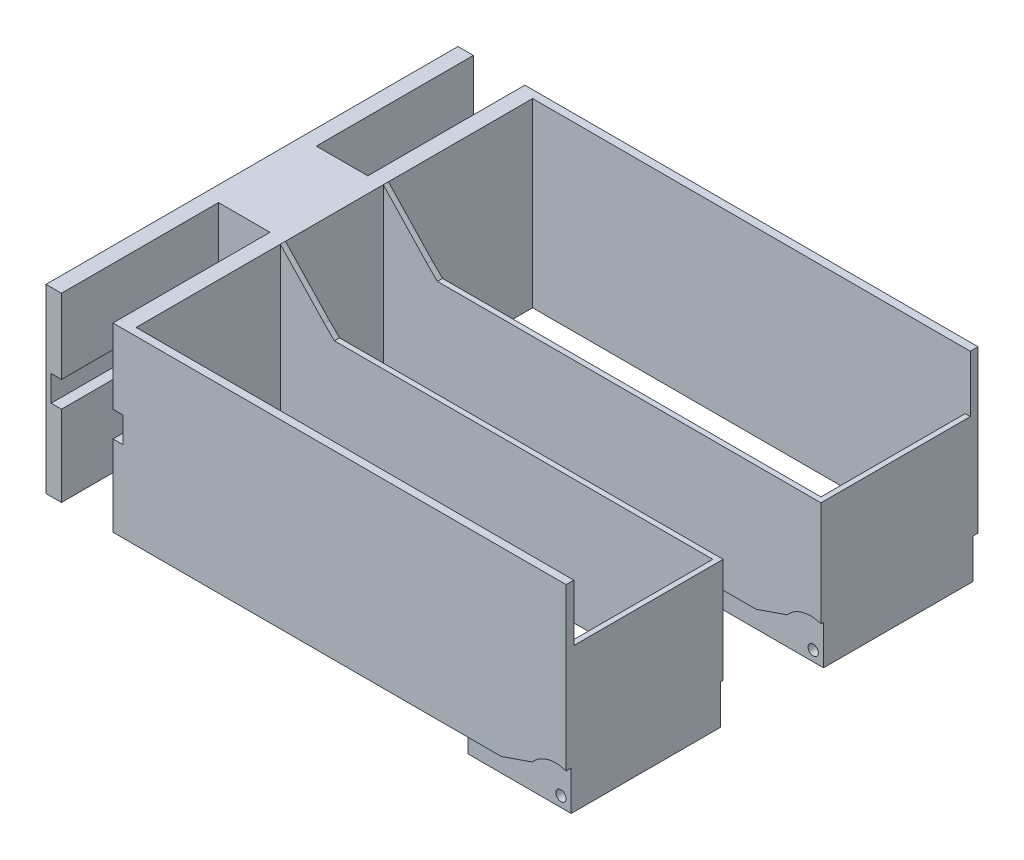
SolidWorks part; units mm, degrees
ref_plane "Front Plane" through (0, 0, 0) normal (0, 0, 1) x (1, 0, 0)
ref_plane "Top Plane" through (0, 0, 0) normal (0, 1, 0) x (1, 0, 0)
ref_plane "Right Plane" through (0, 0, 0) normal (1, 0, 0) x (0, 0, -1)
sketch "Sketch4" plane through (0, 0, 0) normal (0, 0, 1) x (1, 0, 0)
  line L1 (-42.5, -19.5) -> (42.5, -19.5)
  line L2 (-42.5, -19.5) -> (-42.5, 19.5)
  line L3 (-42.5, 19.5) -> (42.5, 19.5)
  line L4 (42.5, -19.5) -> (42.5, 19.5)
  line L5 (-42.5, -19.5) -> (42.5, 19.5) construction
  line L6 (-42.5, 19.5) -> (42.5, -19.5) construction
  point P0 (0, 0)
  dimension "D1" = 39
  dimension "D2" = 85
extrude "Boss-Extrude2" add sketch "Sketch4" along normal blind 30
sketch "Angled cut" plane through (0, 0, 30) normal (0, 0, 1) x (1, 0, 0)
  line L7 (12.07, 10.5) -> (42.5, 10.5)
  line L8 (42.5, -19.5) -> (42.5, 19.5) construction
  line L9 (42.5, 10.5) -> (42.5, 19.5)
  line L10 (42.5, 19.5) -> (-42.5, 19.5)
  line L11 (12.07, 10.5) -> (-34, 10.5)
  line L12 (-42.5, 19.5) -> (-34, 10.5)
  dimension "D1" = 9
  dimension "D2" = 30.43
sketch "Sketch6" plane through (0, 19.5, 0) normal (0, 1, 0) x (1, 0, 0)
  line L1 (42.5, 0) -> (-42.5, 0) construction
  line L2 (-4.9101, 0) -> (-4.9101, 1)
  line L3 (-4.9101, 1) -> (-43.5, 1)
  line L4 (-43.5, 1) -> (-43.5, -30)
  line L5 (-42.5, -30) -> (-43.5, -30)
  line L6 (-42.5, -30) -> (-42.5, 0)
  line L7 (-42.5, 0) -> (-4.9101, 0)
  dimension "D1" = 1
  dimension "D2" = 1
extrude "Boss-Extrude3" add sketch "Sketch6" against normal blind 39
sketch "Sketch7" plane through (0, 19.5, 0) normal (0, 1, 0) x (1, 0, 0)
  line L0 (-0.5, -30) -> (-0.5, -15) construction
  line L1 (42.5, -30) -> (-43.5, -30) construction
  line L2 (42.5, -15) -> (-0.5, -15) construction
  line L3 (42.5, -30) -> (42.5, 0) construction
  line L4 (42.5, 0) -> (-4.9101, 0) construction
  line L5 (-42.5, -29) -> (41.5, -29)
  line L6 (-42.5, -29) -> (-42.5, -1)
  line L7 (-42.5, -1) -> (41.5, -1)
  line L8 (41.5, -29) -> (41.5, -1)
  line L9 (-42.5, -29) -> (41.5, -1) construction
  line L10 (-42.5, -1) -> (41.5, -29) construction
  dimension "D1" = 1
  dimension "D2" = 1
extrude "Cut-Extrude1" cut sketch "Sketch7" against normal blind 39
extrude "Cut-Extrude2" cut sketch "Angled cut" against normal blind 1 contours L7 L9 L10 L12 L11
sketch "Sketch9" plane through (0, 0, 29) normal (0, 0, 1) x (1, 0, 0)
  line L1 (41.5, 19.5) -> (42.5, 19.5)
  line L2 (41.5, 19.5) -> (41.5, 10.5)
  line L3 (41.5, 10.5) -> (42.5, 10.5)
  line L4 (42.5, 19.5) -> (42.5, 10.5)
extrude "Cut-Extrude4" cut sketch "Sketch9" against normal up to vertex (28 mm away) up to point (41.5, 19.5, 1)
sketch "Sketch19" plane through (-43.5, 0, 0) normal (-1, 0, 0) x (0, 0, 1)
  line L1 (-1, 19.5) -> (30, 19.5)
  line L2 (-1, 19.5) -> (-1, -19.5)
  line L3 (-1, -19.5) -> (30, -19.5)
  line L4 (30, 19.5) -> (30, -19.5)
extrude "Boss-Extrude4" add sketch "Sketch19" along normal blind 2
sketch "Sketch20" plane through (0, 0, 30) normal (0, 0, 1) x (1, 0, 0)
  line L1 (-45.5, 19.5) -> (-42.5, 19.5)
  line L2 (-45.5, 19.5) -> (-45.5, -19.5)
  line L3 (-45.5, -19.5) -> (-42.5, -19.5)
  line L4 (-42.5, 19.5) -> (-42.5, -19.5)
extrude "Boss-Extrude5" add sketch "Sketch20" along normal blind 9
sketch "Sketch38" plane through (0, 10.5, 0) normal (0, 1, 0) x (1, 0, 0)
  line L1 (42.5, -30) -> (41.5, -30)
  line L2 (42.5, -30) -> (42.5, -1)
  line L3 (42.5, -1) -> (41.5, -1)
  line L4 (41.5, -30) -> (41.5, -1)
extrude "Boss-Extrude6" add sketch "Sketch38" along normal up to vertex (9 mm away) up to point (42.5, 19.5, 1)
sketch "Sketch39" plane through (-4.9101, 0, 0) normal (1, 0, 0) x (0, 0, -1)
  line L1 (1, 19.5) -> (0, 19.5)
  line L2 (1, 19.5) -> (1, -19.5)
  line L3 (1, -19.5) -> (0, -19.5)
  line L4 (0, 19.5) -> (0, -19.5)
extrude "Boss-Extrude7" add sketch "Sketch39" along normal up to vertex (47.4101 mm away) up to point (42.5, 19.5, 0)
sketch "Sketch40" plane through (0, 0, 29) normal (0, 0, -1) x (-1, 0, 0)
  line L0 (-42.5, -19.5) -> (-42.5, 0)
  line L1 (-42.5, -19.5) -> (-42.5, 19.5) construction
  line L2 (-42.5, 0) -> (-22.5, -19.5)
  line L3 (-42.5, -19.5) -> (45.5, -19.5) construction
  line L4 (-22.5, -19.5) -> (-42.5, -19.5)
  dimension "D1" = 20
extrude "Boss-Extrude8" add sketch "Sketch40" along normal up to vertex (28 mm away) up to point (41.5, -19.5, 1)
sketch "Sketch42" plane through (0, 0, -1) normal (0, 0, -1) x (-1, 0, 0)
  line L0 (45.5, 19.5) -> (45.5, -19.5) construction
  line L1 (45.5, 0) -> (43.5, 0)
  line L2 (45.5, 0) -> (45.5, 5)
  line L3 (45.5, 5) -> (43.5, 5)
  line L4 (43.5, 0) -> (43.5, 5)
  dimension "D1" = 5
  dimension "D2" = 2
extrude "Cut-Extrude5" cut sketch "Sketch42" against normal blind 30
sketch "Sketch44" plane through (0, 0, -1) normal (0, 0, 1) x (1, 0, 0)
  line L0 (-42.5, -19.5) -> (42.5, -19.5) construction
  line L1 (42.5, -19.5) -> (42.5, 19.5) construction
  circle A0 centre (40.5, -17.5) radius 1
  dimension "D2" = 2
  dimension "D1" = 2
  dimension "D3" = 2
sketch "Sketch45" plane through (0, 0, 30) normal (0, 0, 1) x (1, 0, 0)
  line L0 (-42.5, 19.5) -> (-42.5, -19.5)
  line L1 (-42.5, -19.5) -> (42.5, -19.5)
  line L2 (42.5, -19.5) -> (42.5, 19.5)
  line L3 (42.5, 19.5) -> (41.5, 19.5)
  line L4 (41.5, 19.5) -> (41.5, 10.5)
  line L5 (41.5, 10.5) -> (-34, 10.5)
  line L6 (-34, 10.5) -> (-42.5, 19.5)
extrude "Boss-Extrude9" add sketch "Sketch45" along normal blind 1
extrude "Cut-Extrude7" cut sketch "Sketch44" along normal up to vertex (32 mm away) contours A0 up to point (42.5, -19.5, 31)
sketch "Sketch46" plane through (0, 0, 31) normal (0, 0, 1) x (1, 0, 0)
  line L0 (42.5, -19.5) -> (42.5, 19.5) construction
  line L2 (-42.5, -19.5) -> (42.5, -19.5)
  line L3 (-42.5, -19.5) -> (-42.5, -15.6964)
  line L4 (-42.5, -15.6964) -> (42.5, -15.6964)
  line L5 (42.5, -19.5) -> (42.5, -15.6964)
extrude "Cut-Extrude8" cut sketch "Sketch46" against normal blind 1
sketch "Sketch47" plane through (0, 19.5, 0) normal (0, 1, 0) x (1, 0, 0)
  line L0 (41.5, -15) -> (-45.5, -15) construction
  line L1 (41.5, -29) -> (41.5, -1) construction
  line L2 (-45.5, -39) -> (-45.5, 1) construction
ref_plane "Plane1" through (0, 0, 15) normal (0, 0, 1) x (1, 0, 0)
mirror "Mirror1" about plane through (0, 0, 15) normal (0, 0, 1) of "Cut-Extrude8"
sketch "Sketch48" plane through (0, 0, 29) normal (0, 0, -1) x (-1, 0, 0)
  line L0 (42.5, -15.6964) -> (42.5, -19.5) construction
  line L5 (42.5, -17.5982) -> (-22.5, -17.5982)
  line L6 (42.5, -17.5982) -> (42.5, -19.5)
  line L7 (42.5, -19.5) -> (-22.5, -19.5)
  line L8 (-22.5, -17.5982) -> (-22.5, -19.5)
extrude "Cut-Extrude9" cut sketch "Sketch48" along normal up to vertex (29 mm away) and the other way up to vertex (1 mm away) up to point (-42.5, -19.5, 0) other way up to point (42.5, -19.5, 30)
sketch "Sketch49" plane through (0, 0, -1) normal (0, 0, -1) x (-1, 0, 0)
  circle A0 centre (-40.5, -17.5) radius 6
  dimension "D1" = 12
extrude "Cut-Extrude10" cut sketch "Sketch49" against normal blind 1
chamfer "Chamfer1" distance 5 angle 40 1 edges at (34.7775, -15.6964, -0.5) first distance on face at (38.23, -12.9505, -0.5)
mirror "Mirror5" about plane through (0, 0, 15) normal (0, 0, 1) of "Cut-Extrude10"
chamfer "Chamfer2" distance 5 angle 30 1 edges at (34.7775, -15.6964, 30.5) first distance on face at (-3.8613, -15.6964, 30.5)
sketch "Sketch50" plane through (-42.5, 0, 0) normal (1, 0, 0) x (0, 0, -1)
  line L0 (1, -15.6964) -> (1, -19.5) construction
  line L1 (-30, -17.5982) -> (1, -17.5982)
  line L2 (-30, -17.5982) -> (-30, -19.5)
  line L3 (-30, -19.5) -> (1, -19.5)
  line L4 (1, -17.5982) -> (1, -19.5)
extrude "Cut-Extrude11" cut sketch "Sketch50" against normal up to vertex (3 mm away) up to point (-45.5, -19.5, -1)
sketch "Sketch52" plane through (0, 0, 39) normal (0, 0, 1) x (1, 0, 0)
  line L1 (-45.5, 19.5) -> (-42.5, 19.5)
  line L2 (-45.5, 19.5) -> (-45.5, -19.5)
  line L3 (-45.5, -19.5) -> (-42.5, -19.5)
  line L4 (-42.5, 19.5) -> (-42.5, -19.5)
extrude "Boss-Extrude10" add sketch "Sketch52" along normal blind 0.5
ref_plane "Plane3" through (0, 0, 39.5) normal (0, 0, 1) x (1, 0, 0)
mirror "Mirror8" about plane through (0, 0, 39.5) normal (0, 0, 1) of bodies 151
sketch "Sketch56" plane through (42.5, 0, 0) normal (1, 0, 0) x (0, 0, -1)
  line L0 (-31, 19.5) -> (1, 19.5) construction
  line L1 (-31, -15.6964) -> (-30, -15.6964)
  line L2 (-31, -15.6964) -> (-31, 19.5)
  line L3 (-31, 19.5) -> (-30, 19.5)
  line L4 (-30, -15.6964) -> (-30, 19.5)
extrude "Cut-Extrude13" cut sketch "Sketch56" against normal up to vertex (85 mm away) up to point (-42.5, 19.5, 29)
mirror "Mirror11" about plane through (0, 0, 39.5) normal (0, 0, 1) of "Cut-Extrude13"
sketch "Sketch58" plane through (0, 0, -1) normal (0, 0, -1) x (-1, 0, 0)
  line L0 (-41.5, 19.5) -> (45.5, 19.5) construction
  line L1 (45.5, 19.5) -> (-42.5, 19.5)
  line L2 (45.5, 19.5) -> (45.5, -19.5)
  line L3 (45.5, -19.5) -> (-42.5, -19.5)
  line L4 (-42.5, 19.5) -> (-42.5, -19.5)
extrude "Cut-Extrude14" cut sketch "Sketch58" against normal blind 0.5
sketch "Sketch59" plane through (0, 0, 80) normal (0, 0, 1) x (1, 0, 0)
  line L1 (-45.5, 19.5) -> (42.5, 19.5)
  line L2 (-45.5, 19.5) -> (-45.5, -19.5)
  line L3 (-45.5, -19.5) -> (42.5, -19.5)
  line L4 (42.5, 19.5) -> (42.5, -19.5)
extrude "Cut-Extrude15" cut sketch "Sketch59" against normal blind 0.5
sketch "Sketch60" plane through (-45.5, 0, 0) normal (-1, 0, 0) x (0, 0, 1)
  line L0 (79.5, 19.5) -> (-0.5, 19.5) construction
  line L1 (30, -17.5982) -> (49, -17.5982)
  line L2 (30, -17.5982) -> (30, 19.5)
  line L3 (30, 19.5) -> (49, 19.5)
  line L4 (49, -17.5982) -> (49, 19.5)
extrude "Boss-Extrude11" add sketch "Sketch60" along normal blind 10
sketch "Sketch61" plane through (0, 0, 30) normal (0, 0, -1) x (-1, 0, 0)
  line L1 (55.5, 19.5) -> (58.5, 19.5)
  line L2 (55.5, 19.5) -> (55.5, -17.5982)
  line L3 (55.5, -17.5982) -> (58.5, -17.5982)
  line L4 (58.5, 19.5) -> (58.5, -17.5982)
  dimension "D1" = 3
extrude "Boss-Extrude12" add sketch "Sketch61" along normal up to vertex (30.5 mm away) and the other way up to vertex (49.5 mm away) up to point (-45.5, 5, -0.5) other way up to point (-45.5, 19.5, 79.5)
ref_plane "Plane4" through (-50.5, 0, 0) normal (-1, 0, 0) x (0, 0, 1)
mirror "Mirror12" about plane through (-50.5, 0, 0) normal (-1, 0, 0) of "Cut-Extrude5"
mirror "Mirror13" about plane through (0, 0, 39.5) normal (0, 0, 1) of "Mirror12"
sketch "Sketch63" plane through (0, 0, 0) normal (0, 0, -1) x (-1, 0, 0)
  line L1 (42.5, -15.6964) -> (-42.5, -15.6964)
  line L2 (42.5, -15.6964) -> (42.5, -19.5)
  line L3 (42.5, -19.5) -> (-42.5, -19.5)
  line L4 (-42.5, -15.6964) -> (-42.5, -19.5)
extrude "Cut-Extrude16" cut sketch "Sketch63" against normal blind 0.5
mirror "Mirror14" about plane through (0, 0, 15) normal (0, 0, 1) of "Cut-Extrude16"
mirror "Mirror15" about plane through (0, 0, 39.5) normal (0, 0, 1) of "Cut-Extrude16", "Mirror14"
sketch "Sketch66" plane through (0, 0, 0) normal (0, 0, -1) x (-1, 0, 0)
  circle A0 centre (-40.5, -17.5) radius 6
extrude "Cut-Extrude17" cut sketch "Sketch66" against normal blind 0.5
mirror "Mirror16" about plane through (0, 0, 15) normal (0, 0, 1) of "Cut-Extrude17"
mirror "Mirror17" about plane through (0, 0, 39.5) normal (0, 0, 1) of "Cut-Extrude17", "Mirror16"
chamfer "Chamfer3" distance 5 angle 40 1 edges at (34.7775, -15.6964, 0.25) first distance on face at (37.531, -13.2695, 0)
chamfer "Chamfer4" distance 5 angle 40 3 edges at (34.7775, -15.6964, 78.75) (34.7775, -15.6964, 29.75) (34.7775, -15.6964, 49.25) first distance on face at (37.531, -13.2695, 79) first distance on face at (38.23, -12.9505, 29.75) first distance on face at (38.23, -12.9505, 49.25)
sketch "Sketch67" plane through (0, -19.5, 0) normal (0, -1, 0) x (1, 0, 0)
  line L1 (-45.5, 49) -> (-42.5, 49)
  line L2 (-45.5, 49) -> (-45.5, 30)
  line L3 (-45.5, 30) -> (-42.5, 30)
  line L4 (-42.5, 49) -> (-42.5, 30)
extrude "Cut-Extrude18" cut sketch "Sketch67" against normal up to vertex (1.9018 mm away) up to point (-45.5, -17.5982, 49)
sketch "Sketch72" plane through (0, -17.5982, 0) normal (0, -1, 0) x (1, 0, 0)
  line L1 (22.5, 1) -> (-42.5, 1)
  line L2 (22.5, 1) -> (22.5, 0.5)
  line L3 (22.5, 0.5) -> (-42.5, 0.5)
  line L4 (-42.5, 1) -> (-42.5, 0.5)
extrude "Cut-Extrude21" cut sketch "Sketch72" against normal up to vertex (1.9018 mm away) up to point (29.9188, -15.6964, 0.5)
mirror "Mirror19" about plane through (0, 0, 15) normal (0, 0, 1) of "Cut-Extrude21"
mirror "Mirror20" about plane through (0, 0, 39.5) normal (0, 0, 1) of "Cut-Extrude21", "Mirror19"
sketch "Sketch74" plane through (0, 0, 0.5) normal (0, 0, -1) x (-1, 0, 0)
  line L1 (-29.9188, -15.6964) -> (-22.5, -15.6964)
  line L2 (-29.9188, -15.6964) -> (-29.9188, -19.5)
  line L3 (-29.9188, -19.5) -> (-22.5, -19.5)
  line L4 (-22.5, -15.6964) -> (-22.5, -19.5)
extrude "Boss-Extrude13" add sketch "Sketch74" against normal blind 2
mirror "Mirror21" about plane through (0, 0, 15) normal (0, 0, 1) of "Boss-Extrude13"
mirror "Mirror22" about plane through (0, 0, 39.5) normal (0, 0, 1) of "Boss-Extrude13", "Mirror21"
sketch "Sketch79" plane through (-42.5, 0, 0) normal (1, 0, 0) x (0, 0, -1)
  line L1 (-79.5, -15.6964) -> (0.5, -15.6964)
  line L2 (-79.5, -15.6964) -> (-79.5, -17.5982)
  line L3 (-79.5, -17.5982) -> (0.5, -17.5982)
  line L4 (0.5, -15.6964) -> (0.5, -17.5982)
extrude "Cut-Extrude31" cut sketch "Sketch79" against normal up to vertex (16 mm away) up to point (-58.5, -17.5982, 79.5)
sketch "Sketch80" plane through (0, 19.5, 0) normal (0, 1, 0) x (1, 0, 0)
  line L0 (42.5, -30) -> (42.5, 0.5) construction
  line L1 (42.5, -1) -> (41.5, -1)
  line L2 (42.5, -1) -> (42.5, -30)
  line L3 (42.5, -30) -> (41.5, -30)
  line L4 (41.5, -1) -> (41.5, -30)
sketch "Sketch81" plane through (0, 10.5, 0) normal (0, 1, 0) x (1, 0, 0)
  line L1 (-34, -29) -> (60, -29)
  line L2 (-34, -29) -> (-34, -30)
  line L3 (-34, -30) -> (60, -30)
  line L4 (60, -29) -> (60, -30)
  point P6 (0, 0)
  point P7 (0, 0)
  dimension "D1" = 94
extrude "Cut-Extrude33" cut sketch "Sketch81" against normal blind 2
extrude "Cut-Extrude34" cut sketch "Sketch80" against normal up to vertex (11 mm away) up to point (41.5, 8.5, 29)
chamfer "Chamfer5" distance 2 angle 45 1 edges at (-34, 8.5, 29.5)
mirror "Mirror23" about plane through (0, 0, 39.5) normal (0, 0, 1) of "Cut-Extrude31", "Cut-Extrude33", "Cut-Extrude34", "Chamfer5"
